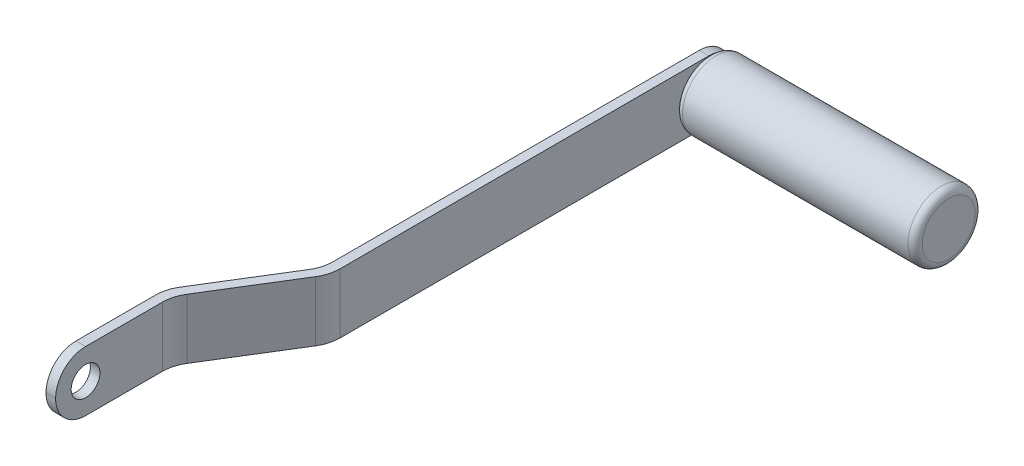
SolidWorks part; units mm, degrees
material "Nickel"
ref_plane "Front Plane" through (0, 0, 0) normal (0, 0, 1) x (1, 0, 0)
ref_plane "Top Plane" through (0, 0, 0) normal (0, 1, 0) x (1, 0, 0)
ref_plane "Right Plane" through (0, 0, 0) normal (1, 0, 0) x (0, 0, -1)
sketch "Sketch1" plane through (0, 0, 0) normal (0, 1, 0) x (1, 0, 0)
  line L0 (0, 0) -> (0, 50)
  line L1 (0, 50) -> (25, 90.4992)
  line L2 (25, 90.4992) -> (25, 260)
  dimension "D1" = 50
  dimension "D2" = 260
  dimension "D3" = 25
extrude "Extrude-Thin1" add sketch "Sketch1" along normal blind 25 thin thin type one direction wall 4
fillet "Fillet1" radius 15 4 edges at (29, 12.5, -89.364) (25, 12.5, -90.4992) (0, 12.5, -50) (4, 12.5, -48.8648)
fillet "Fillet2" radius 12.5 4 edges at (27, 0, -260) (27, 25, -260) (2, 0, 0) (2, 25, 0)
sketch "Sketch2" plane through (0, 0, 0) normal (-1, 0, 0) x (0, 0, 1)
  circle A0 centre (-12.5, 12.5) radius 6
  dimension "D1" = 12
extrude "Cut-Extrude1" cut sketch "Sketch2" against normal blind 10
sketch "Sketch3" plane through (29, 0, 0) normal (1, 0, 0) x (0, 0, -1)
  circle A0 centre (247.5, 12.5) radius 14
  dimension "D1" = 28
extrude "Boss-Extrude1" add sketch "Sketch3" along normal blind 100 separate body
fillet "Fillet3" radius 3 2 edges at (129, 12.5, -261.5) (29, 12.5, -261.5)
